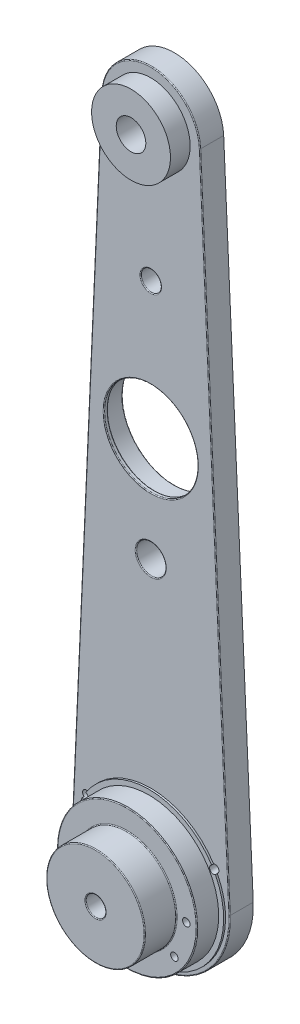
SolidWorks part; units mm, degrees
ref_plane "Front Plane" through (0, 0, 0) normal (0, 0, 1) x (1, 0, 0)
ref_plane "Top Plane" through (0, 0, 0) normal (0, 1, 0) x (1, 0, 0)
ref_plane "Right Plane" through (0, 0, 0) normal (1, 0, 0) x (0, 0, -1)
sketch "Sketch1" plane through (0, 0, 0) normal (0, 0, 1) x (1, 0, 0)
  line L0 (0, 209.417) -> (0, 0) construction
  line L1 (25.3737, 1.1553) -> (15.8586, 210.1391)
  line L2 (-15.8586, 210.1391) -> (-25.3737, 1.1553)
  circle A1 centre (0, 209.417) radius 4.7625
  arc A2 (-15.8586, 210.1391) -> (15.8586, 210.1391) centre (0, 209.417) cw
  arc A3 (-25.3737, 1.1553) -> (25.3737, 1.1553) centre (0, 0) ccw
  dimension "D2" = 15.875
  dimension "D3" = 25.4
  dimension "D4" = 9.525
  dimension "D1" = 209.417
extrude "Boss-Extrude1" add sketch "Sketch1" along normal mid plane 7.62
sketch "Sketch2" plane through (0, 0, 3.81) normal (0, 0, 1) x (1, 0, 0)
  circle A0 centre (0, 0) radius 22.5
  dimension "D1" = 45
extrude "Boss-Extrude2" add sketch "Sketch2" along normal blind 7.62
sketch "Sketch3" plane through (0, 0, 3.81) normal (0, 0, 1) x (1, 0, 0)
  circle A0 centre (0, 0) radius 24.0899
extrude "Boss-Extrude3" add sketch "Sketch3" along normal offset from surface (0.62 mm away) 7 up to face at (22.5, 0, 11.43)
sketch "Sketch4" plane through (0, 0, 3.81) normal (0, 0, 1) x (1, 0, 0)
  circle A0 centre (0, 87.917) radius 4.7625
  circle A1 centre (0, 121.5) radius 16.6688
  circle A2 centre (0, 209.417) radius 4.7625 construction
  dimension "D2" = 9.525
  dimension "D3" = 33.3375
  dimension "D1" = 87.917
  dimension "D4" = 87.917
extrude "Cut-Extrude1" cut sketch "Sketch4" against normal through all both and the other way through all
sketch "Sketch5" plane through (0, 0, 0) normal (0, 0, 1) x (1, 0, 0)
  line L0 (-155.5635, 76.3042) -> (0, 231.8677)
  line L1 (-155.5635, 76.3042) -> (0, -79.2593)
  line L2 (0, 231.8677) -> (155.5635, 76.3042)
  line L3 (0, -79.2593) -> (155.5635, 76.3042)
  line L4 (-155.5635, 76.3042) -> (155.5635, 76.3042) construction
  line L5 (0, 231.8677) -> (0, -79.2593) construction
  arc A1 (15.8586, 210.1391) -> (-15.8586, 210.1391) centre (0, 209.417) ccw construction
  point P1 (0, 76.3042)
  dimension "D1" = 220
sketch "Sketch6" plane through (0, 0, 3.81) normal (0, 0, 1) x (1, 0, 0)
  circle A0 centre (0, 121.5) radius 16.6688
  circle A1 centre (0, 121.5) radius 15.0813
  circle A2 centre (0, 121.5) radius 16.6688 construction
  dimension "D1" = 1.5875
extrude "Boss-Extrude4" add sketch "Sketch6" against normal offset from surface (1.27 mm away) 6.35 up to face at (4.7625, 87.917, -3.81)
sketch "Sketch7" plane through (0, 0, -3.81) normal (0, 0, -1) x (-1, 0, 0)
  line L0 (11, -20.6542) -> (11, 7.5625) construction
  line L1 (-11.7938, -25.4) -> (11.7937, -25.4)
  line L2 (-11.7938, -25.4) -> (-11.7938, 8.3563)
  line L3 (-11.7938, 8.3563) -> (11.7937, 8.3563)
  line L4 (11.7937, -25.4) -> (11.7937, 8.3563)
  line L5 (-11.7938, -25.4) -> (11.7937, 8.3563) construction
  line L6 (-11.7938, 8.3563) -> (11.7937, -25.4) construction
  line L7 (11, 7.5625) -> (-11, 7.5625) construction
  arc A0 (-25.3737, 1.1553) -> (25.3737, 1.1553) centre (0, 0) ccw construction
  point P0 (0, -8.5219)
  dimension "D1" = 0.7937
  dimension "D2" = 0.7937
extrude "Cut-Extrude2" cut sketch "Sketch7" against normal blind 2.54
sketch "Sketch8" plane through (0, 0, -1.27) normal (0, 0, -1) x (-1, 0, 0)
  circle A0 centre (-9, 5.5625) radius 0.95
  circle A1 centre (9, 5.5625) radius 0.95
  circle A2 centre (9, -5.5625) radius 0.95
  circle A3 centre (-9, -5.5625) radius 0.95
  dimension "D1" = 1.9
extrude "Cut-Extrude3" cut sketch "Sketch8" against normal through all
sketch "Sketch9" plane through (0, 0, 3.81) normal (0, 0, 1) x (1, 0, 0)
  circle A0 centre (0, 209.417) radius 12.7
  circle A1 centre (0, 209.417) radius 4.7625 construction
  circle A2 centre (0, 209.417) radius 4.7625
  dimension "D1" = 25.4
extrude "Boss-Extrude5" add sketch "Sketch9" along normal blind 6.35
sketch "Sketch10" plane through (0, 0, 11.43) normal (0, 0, 1) x (1, 0, 0)
  circle A0 centre (0, 0) radius 15.875
  dimension "D1" = 31.75
extrude "Boss-Extrude6" add sketch "Sketch10" along normal blind 10.16
sketch "Sketch11" plane through (0, 0, -3.81) normal (0, 0, -1) x (-1, 0, 0)
  circle A0 centre (-20.7431, 11.983) radius 1.2
  circle A1 centre (20.7431, 11.983) radius 1.2
  circle A2 centre (19.0618, 0) radius 1.2
  circle A3 centre (15.2212, -11.4747) radius 1.2
  circle A4 centre (-15.2212, -11.4747) radius 1.2
  circle A5 centre (-19.0618, 0) radius 1.2
  dimension "D1" = 2.4
extrude "Cut-Extrude4" cut sketch "Sketch11" against normal through all both and the other way through all
sketch "Sketch12" plane through (0, 0, 3.81) normal (0, 0, 1) x (1, 0, 0)
  line L3 (0, 121.5) -> (0, 209.417) construction
  circle A7 centre (0, 121.5) radius 15.0813 construction
  circle A8 centre (0, 209.417) radius 4.7625 construction
  circle A9 centre (0, 165.4585) radius 3.2385
  dimension "D1" = 6.477
extrude "Cut-Extrude5" cut sketch "Sketch12" against normal through all
sketch "Sketch13" plane through (0, 0, -1.27) normal (0, 0, -1) x (-1, 0, 0)
  circle A0 centre (0, 0) radius 3.175
  dimension "D1" = 6.35
extrude "Cut-Extrude6" cut sketch "Sketch13" against normal through all both and the other way through all
sketch "Sketch14" plane through (0, 0, -1.27) normal (0, 0, -1) x (-1, 0, 0)
  circle A0 centre (0, 0) radius 4
  dimension "D1" = 8
extrude "Cut-Extrude7" cut sketch "Sketch14" against normal blind 12.7
fillet "Fillet1" radius 0.254 16 edges at (15.875, 0, 11.43) (22.5, 0, 11.43) (-4, 0, -1.27) (-3.175, 0, 21.59) (-4.7625, 87.917, 3.81) (15.0813, 121.5, 3.81) (3.2385, 165.4585, 3.81) (3.2385, 165.4585, -3.81) (4.7625, 87.917, -3.81) (-15.0813, 121.5, 2.54) (16.6688, 121.5, -3.81) (0, -25.4, 3.81) (-20.6161, 105.6472, 3.81) (0, 225.292, 3.81) (15.875, 0, 21.59) (20.6161, 105.6472, 3.81)
equation "\"UpperLinkLength\"= \"LowerFirstStage\" + \"LowerSecondStage\""
equation "\"LowerFirstStage\"= \"60T_20T_122B\""
equation "\"LowerSecondStage\"= \"60T_20T_100B\""
equation "\"D1@Sketch1\"=\"UpperLinkLength\""
equation "\"UpperStage\"= \"60T_20T_100B\""
equation "\"60T_20T_100B\"= 3.4613"
equation "\"60T_20T_125B\"= 4.9626"
equation "\"D1@Sketch4\"=\"UpperStage\""
equation "\"D4@Sketch4\"=\"LowerSecondStage\""
equation "\"60T_20T_122B\"= 121.5mm"
